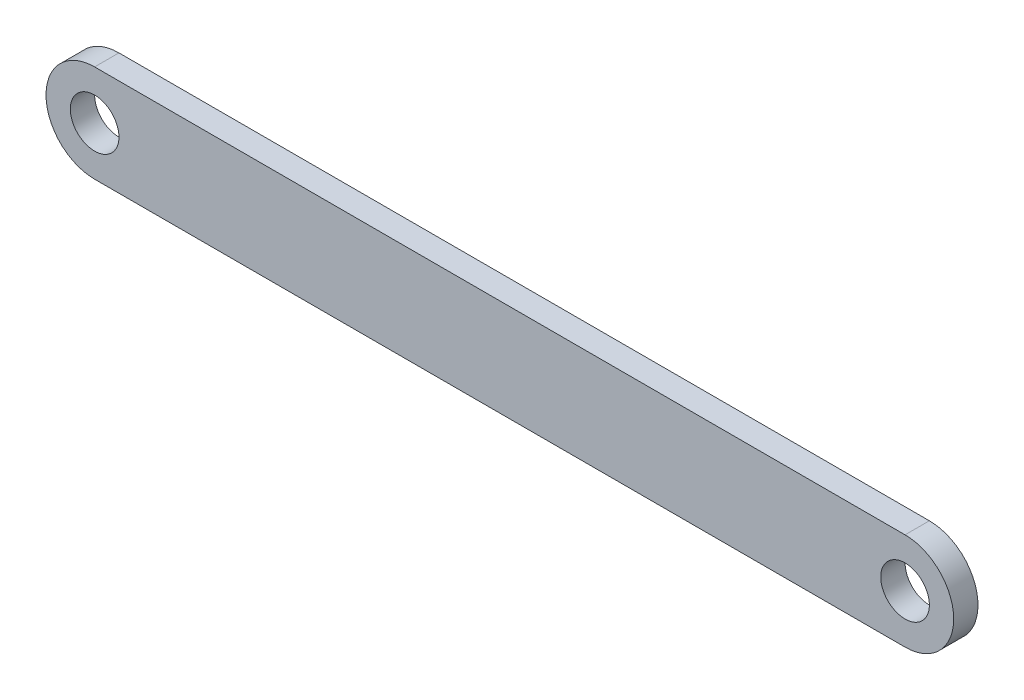
SolidWorks part; units mm, degrees
ref_plane "Front Plane" through (0, 0, 0) normal (0, 0, 1) x (1, 0, 0)
ref_plane "Top Plane" through (0, 0, 0) normal (0, 1, 0) x (1, 0, 0)
ref_plane "Right Plane" through (0, 0, 0) normal (1, 0, 0) x (0, 0, -1)
sketch "Sketch1" plane through (0, 0, 0) normal (0, 0, 1) x (1, 0, 0)
  line L0 (-50, 0) -> (50, 0) construction
  line L1 (-50, 6) -> (50, 6)
  line L2 (-50, -6) -> (50, -6)
  arc A0 (-50, 6) -> (-50, -6) centre (-50, 0) ccw
  arc A1 (50, -6) -> (50, 6) centre (50, 0) ccw
  circle A2 centre (-50, 0) radius 3
  circle A3 centre (50, 0) radius 3
  point P3 (0, 0)
  point P12 (-33.9383, 5)
  dimension "D1" = 6
  dimension "D2" = 6
  dimension "D3" = 100
extrude "Boss-Extrude1" add sketch "Sketch1" along normal blind 3
